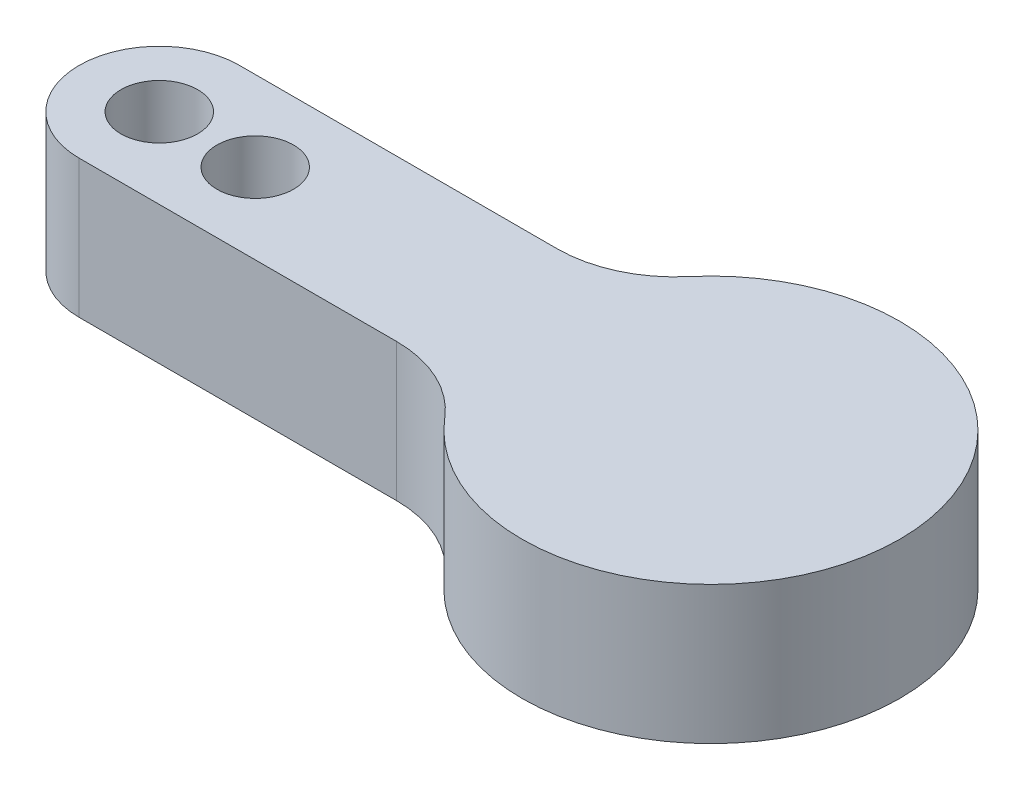
SolidWorks part; units mm, degrees
ref_plane "Front Plane" through (0, 0, 0) normal (0, 0, 1) x (1, 0, 0)
ref_plane "Top Plane" through (0, 0, 0) normal (0, 1, 0) x (1, 0, 0)
ref_plane "Right Plane" through (0, 0, 0) normal (1, 0, 0) x (0, 0, -1)
sketch "Sketch1" plane through (0, 0, 0) normal (0, 1, 0) x (1, 0, 0)
  line L1 (-23.368, 3.4) -> (-9.9217, 3.4)
  line L2 (-23.368, -3.4) -> (-9.9217, -3.4)
  arc A8 (-6.1057, -5.1692) -> (-6.1057, 5.1692) centre (0, 0) ccw
  circle A9 centre (-19.304, 0) radius 1.625
  circle A10 centre (-23.368, 0) radius 1.625
  arc A11 (-23.368, 3.4) -> (-23.368, -3.4) centre (-23.368, 0) ccw
  arc A12 (-9.9217, -3.4) -> (-6.1057, -5.1692) centre (-9.9217, -8.4) cw
  arc A13 (-9.9217, 3.4) -> (-6.1057, 5.1692) centre (-9.9217, 8.4) ccw
  point P1 (0, 0)
  point P2 (0, 0)
  point P9 (0, 0)
  point P12 (0, 0)
  point P15 (0, 0)
  point P16 (0, 0)
  point P17 (0, 0)
  point P18 (0, 0)
  point P19 (0, 0)
  point P20 (0, 0)
  point P21 (-8.3575, -3.3678)
  point P25 (0, 0)
  dimension "D6" = 6.8
  dimension "D7" = 5
  dimension "D1" = 16
  dimension "D2" = 3.25
  dimension "D3" = 3.25
  dimension "D4" = 19.304
  dimension "D5" = 23.368
extrude "Boss-Extrude1" add sketch "Sketch1" along normal blind 5.842 contours A13 L1 A11 L2 A12 A8 A10 A9 region at (-5.6745, 0, 0)
